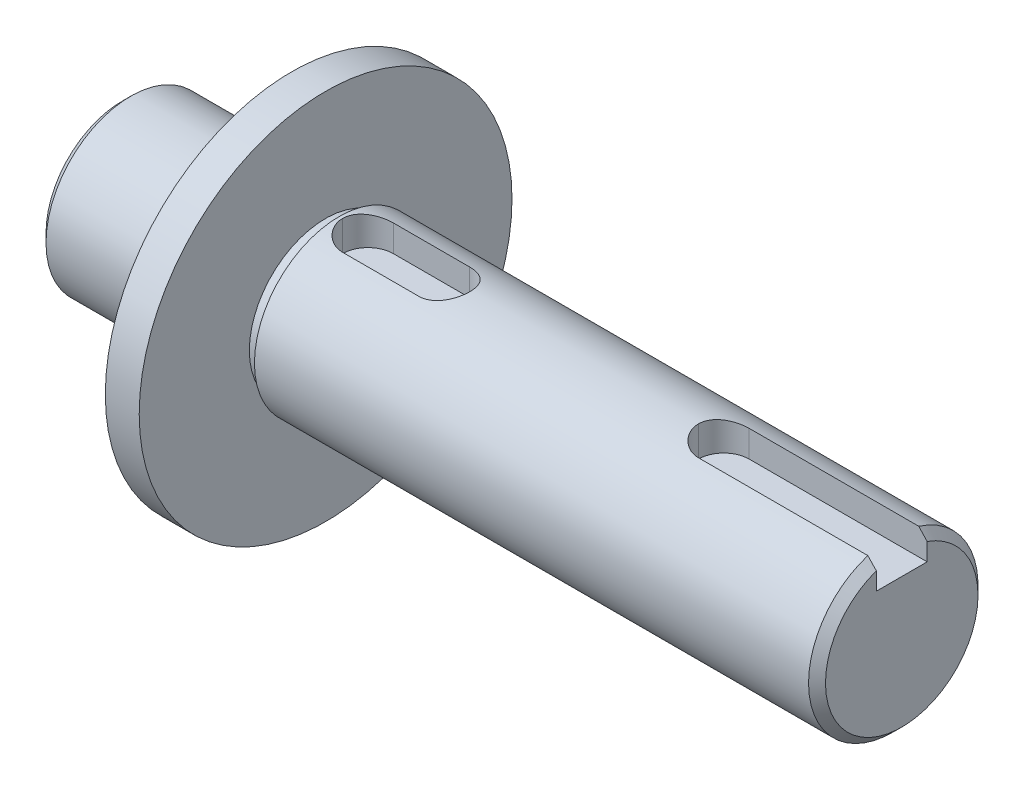
SolidWorks part; units mm, degrees
material "6061-T6 (SS)"
ref_plane "Front Plane" through (0, 0, 0) normal (0, 0, 1) x (1, 0, 0)
ref_plane "Top Plane" through (0, 0, 0) normal (0, 1, 0) x (1, 0, 0)
ref_plane "Right Plane" through (0, 0, 0) normal (1, 0, 0) x (0, 0, -1)
sketch "Sketch1" plane through (0, 0, 0) normal (1, 0, 0) x (0, 0, -1)
  circle A0 centre (0, 0) radius 5
  dimension "D1" = 10
extrude "Boss-Extrude1" add sketch "Sketch1" along normal blind 34
chamfer "Chamfer1" distance 0.5 angle 45 1 edges at (34, 0, -5)
sketch "Sketch2" plane through (0, 0, 0) normal (-1, 0, 0) x (0, 0, 1)
  circle A0 centre (0, 0) radius 11
  dimension "D1" = 22
extrude "Boss-Extrude2" add sketch "Sketch2" along normal blind 2
sketch "Sketch3" plane through (34, 0, 0) normal (1, 0, 0) x (0, 0, -1)
  line L0 (0, 0) -> (0, 3.2) construction
  line L1 (-1.5, 5) -> (1.5, 5)
  line L2 (-1.5, 5) -> (-1.5, 3.2)
  line L3 (-1.5, 3.2) -> (1.5, 3.2)
  line L4 (1.5, 5) -> (1.5, 3.2)
  line L5 (0, 0) -> (8.3936, 0) construction
  line L6 (-1.5, -3.2) -> (1.5, -3.2)
  line L7 (1.5, -5) -> (1.5, -3.2)
  line L8 (-1.5, -5) -> (1.5, -5)
  line L9 (-1.5, -5) -> (-1.5, -3.2)
  circle A0 centre (0, 0) radius 5 construction
  dimension "D1" = 3
  dimension "D2" = 1.8
extrude "Cut-Extrude1" cut sketch "Sketch3" against normal blind 12 contours L3 L4 L1 L2
fillet "Fillet1" radius 1.5 2 edges at (22, 3.9848, 1.5) (22, 3.9848, -1.5)
sketch "Sketch4" plane through (-2, 0, 0) normal (-1, 0, 0) x (0, 0, 1)
  circle A0 centre (0, 0) radius 5
  dimension "D1" = 10
extrude "Boss-Extrude3" add sketch "Sketch4" along normal blind 10
sketch "Sketch6" plane through (0, 0, 0) normal (0, 0, 1) x (1, 0, 0)
  line L0 (0, 0) -> (37.6174, 0) construction
  line L1 (-2, 5) -> (-2.8, 5)
  line L2 (-2, 5) -> (-2, 4.5)
  line L3 (-2, 4.5) -> (-2.8, 4.5)
  line L4 (-2.8, 5) -> (-2.8, 4.5)
  line L6 (0, 5) -> (0.8, 5)
  line L7 (0, 5) -> (0, 4.5)
  line L8 (0, 4.5) -> (0.8, 4.5)
  line L9 (0.8, 5) -> (0.8, 4.5)
  dimension "D1" = 0.8
  dimension "D2" = 0.5
revolve "Cut-Revolve1" cut sketch "Sketch6" angle 360 about L0
ref_plane "Plane1" through (1, 0, 0) normal (1, 0, 0) x (0, 0, -1)
extrude "Cut-Extrude2" cut sketch "Sketch3<2>" along normal blind 7.5 from surface starting at plane "Plane1"
sketch "Sketch3<2>" plane through (34, 0, 0) normal (1, 0, 0) x (0, 0, -1) same geometry as "Sketch3"
fillet "Fillet3" radius 1.5 8 edges at (1, 3.9848, 1.5) (1, 3.9848, -1.5) (8.5, 3.9848, 1.5) (8.5, 3.9848, -1.5) (1, -3.9848, -1.5) (1, -3.9848, 1.5) (8.5, -3.9848, -1.5) (8.5, -3.9848, 1.5)
chamfer "Chamfer2" distance 0.5 angle 45 1 edges at (-12, 0, 5)
